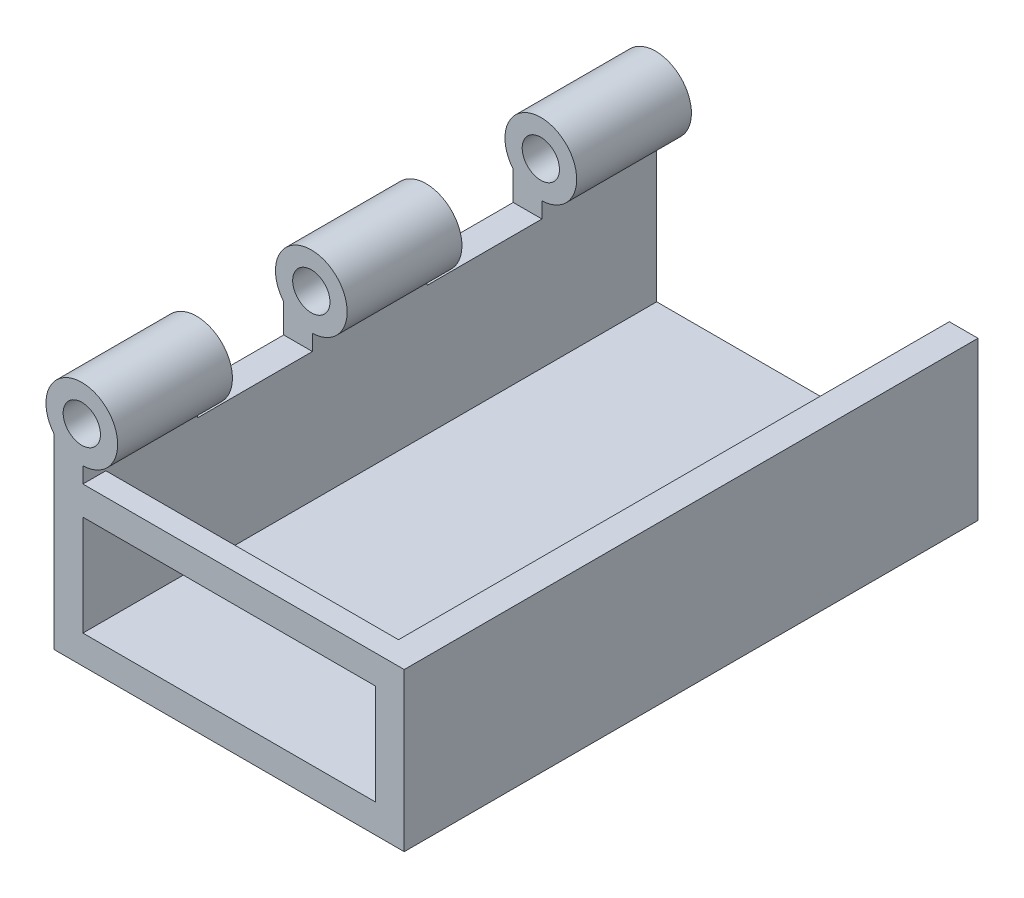
SolidWorks part; units mm, degrees
ref_plane "Front" through (0, 0, 0) normal (0, 0, 1) x (1, 0, 0)
ref_plane "Top" through (0, 0, 0) normal (0, 1, 0) x (1, 0, 0)
ref_plane "Right" through (0, 0, 0) normal (1, 0, 0) x (0, 0, -1)
sketch "Sketch1" plane through (0, 0, 0) normal (0, 1, 0) x (1, 0, 0)
  line L0 (-12.954, 24.384) -> (-15.494, 24.384)
  line L1 (-12.954, 24.384) -> (12.954, 24.384)
  line L2 (-12.954, 24.384) -> (-12.954, -24.384)
  line L3 (-12.954, -24.384) -> (12.954, -24.384)
  line L4 (12.954, 24.384) -> (12.954, -24.384)
  line L5 (-12.954, 24.384) -> (12.954, -24.384) construction
  line L6 (-12.954, -24.384) -> (12.954, 24.384) construction
  line L7 (-15.494, 24.384) -> (-15.494, -26.416)
  line L8 (-15.494, -26.416) -> (15.494, -26.416)
  line L9 (15.494, -26.416) -> (15.494, 24.384)
  line L10 (15.494, 24.384) -> (12.954, 24.384)
  point P0 (0, 0)
  dimension "D1" = 48.768
  dimension "D2" = 25.908
  dimension "D3" = 2.54
  dimension "D4" = 2.54
  dimension "D5" = 2.032
extrude "battery-wall" add sketch "Sketch1" along normal blind 13.97 contours L9 L10 L4 L3 L2 L0 L7 L8 region at (-13.5491, 0, 0)
extrude "battery-base" add sketch "Sketch1<4>" along normal blind 2.54 contours L2 L3 L4 L1
sketch "Sketch1<4>" plane through (0, 0, 0) normal (0, 1, 0) x (1, 0, 0) same geometry as "Sketch1"
sketch "Sketch3" plane through (0, 0, 26.416) normal (0, 0, 1) x (1, 0, 0)
  line L0 (-15.494, 0) -> (15.494, 0) construction
  line L1 (-12.954, 11.43) -> (12.954, 11.43)
  line L2 (-12.954, 11.43) -> (-12.954, 2.54)
  line L3 (-12.954, 2.54) -> (12.954, 2.54)
  line L4 (12.954, 11.43) -> (12.954, 2.54)
  line L5 (-12.954, 11.43) -> (12.954, 2.54) construction
  line L6 (-12.954, 2.54) -> (12.954, 11.43) construction
  line L7 (-15.494, 13.97) -> (-15.494, 0) construction
  line L8 (15.494, 13.97) -> (15.494, 0) construction
  line L9 (-15.494, 13.97) -> (15.494, 13.97) construction
  point P0 (0, 6.985)
  dimension "D1" = 2.54
  dimension "D2" = 2.54
  dimension "D3" = 2.54
  dimension "D4" = 2.54
extrude "battery-gap" cut sketch "Sketch3" against normal blind 2.54
sketch "Sketch4" plane through (0, 0, 26.416) normal (0, 0, 1) x (1, 0, 0)
  line L0 (-12.954, 13.97) -> (-12.954, 11.43) construction
  line L1 (-15.494, 13.97) -> (-12.954, 13.97)
  line L2 (-15.494, 13.97) -> (-15.494, 16.51)
  line L3 (-15.494, 16.51) -> (-12.954, 16.51)
  line L4 (-12.954, 13.97) -> (-12.954, 16.51)
  circle A0 centre (-13.0524, 18.5396) radius 3.175
  circle A1 centre (-13.0524, 18.5396) radius 1.651
  line M12 (15.494, 13.97) -> (-15.494, 13.97)
  dimension "D2" = 6.35
  dimension "D4" = 1.524
  dimension "D1" = 2.54
  dimension "D3" = 2.032
extrude "battery-hinge" add sketch "Sketch4" against normal blind 10.16 contours A0 L2 L4 M12 | L3 A0 L4 | L4 A0 L3 A1 region at (-14.3566, 14.8665, 26.416) region at (-14.1009, 21.4412, 26.416) region at (-13.9406, 16.0381, 26.416)
pattern_linear "LPattern1" count 3 spacing 20.32 along (0, 0, -1) of "battery-hinge"
